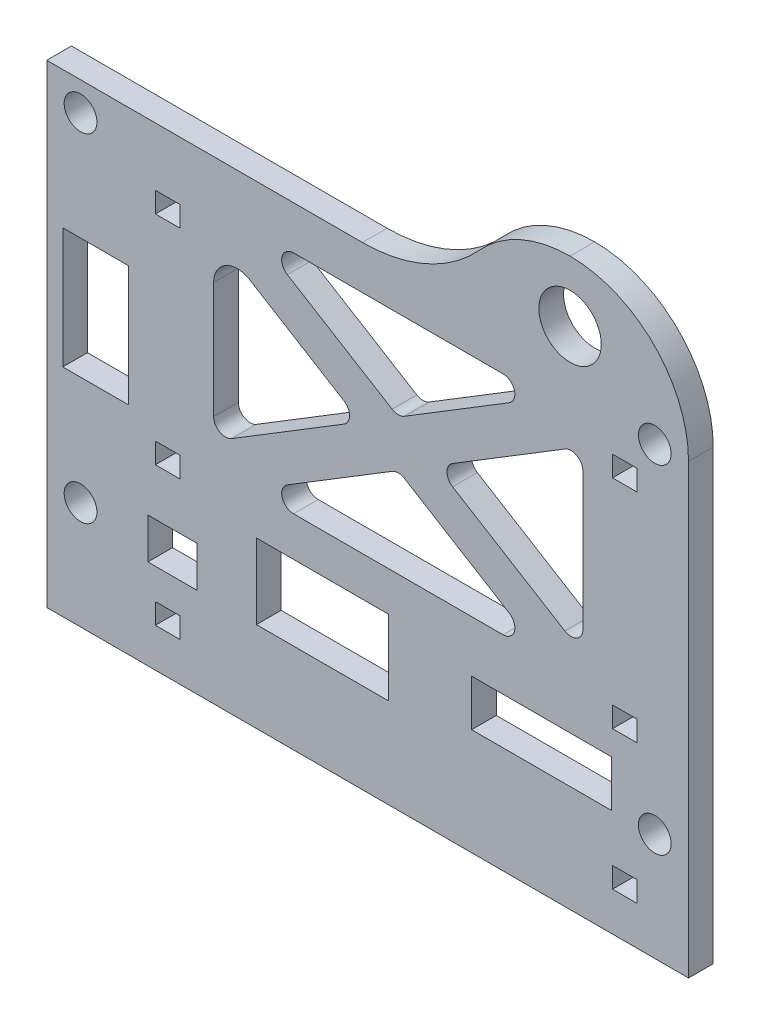
SolidWorks part; units mm, degrees
material "Beech"
ref_plane "Front Plane" through (0, 0, 0) normal (0, 0, 1) x (1, 0, 0)
ref_plane "Top Plane" through (0, 0, 0) normal (0, 1, 0) x (1, 0, 0)
ref_plane "Right Plane" through (0, 0, 0) normal (1, 0, 0) x (0, 0, -1)
sketch "Sketch1" plane through (0, 0, 0) normal (0, 0, 1) x (1, 0, 0)
  line L0 (-20.6375, 0) -> (20.6375, 0)
  line L2 (-20.6375, 0) -> (20.6375, 0)
  line L3 (-20.6375, 0) -> (-20.6375, -5.08)
  line L4 (-20.6375, -5.08) -> (20.6375, -5.08)
  line L5 (20.6375, 0) -> (20.6375, -5.08)
  line L44 (0, 14.605) -> (0, 24.13) construction
  line L46 (-20.6375, 0) -> (-20.6375, 25.4)
  line L47 (-20.6375, 25.4) -> (20.6375, 25.4)
  line L48 (20.6375, 0) -> (20.6375, 25.4)
  line L49 (-20.6375, 12.7) -> (20.6375, 12.7) construction
  circle A2 centre (-18.4658, 23.5585) radius 1.0541
  circle A3 centre (-18.4658, 1.8415) radius 1.0541
  circle A4 centre (18.4658, 1.8415) radius 1.0541
  circle A5 centre (18.4658, 23.5585) radius 1.0541
  point P0 (0, 0)
  point P56 (0, 12.7)
  point P60 (0, 25.4)
  dimension "D14" = 12.7
  dimension "D4" = 2.1082
  dimension "D2" = 5.08
  dimension "D3" = 25.4
  dimension "D12" = 41.275
  dimension "D5" = 2.1717
  dimension "D6" = 1.8415
extrude "Boss-Extrude1" add sketch "Sketch1" along normal blind 1.5875 contours L48 L47 L46 | L5 L0 L3 L4 region at (0, 12.7, 0) region at (0, -2.54, 0)
sketch "Sketch3" plane through (0, 0, 0) normal (0, 0, -1) x (-1, 0, 0)
  line L0 (-15.748, 20.3318) -> (-15.748, 21.6526) construction
  line L1 (-15.748, 21.6526) -> (-17.3355, 21.6526) construction
  line L2 (-17.3355, 21.6526) -> (-17.3355, 20.3318) construction
  line L3 (-17.3355, 20.3318) -> (-15.748, 20.3318) construction
  line L4 (-15.748, 6.3618) -> (-15.748, 7.6826) construction
  line L5 (-15.748, 7.6826) -> (-17.3355, 7.6826) construction
  line L6 (-17.3355, 7.6826) -> (-17.3355, 6.3618) construction
  line L7 (-17.3355, 6.3618) -> (-15.748, 6.3618) construction
  line L8 (-15.748, -2.579) -> (-15.748, -1.2582) construction
  line L9 (-15.748, -1.2582) -> (-17.3355, -1.2582) construction
  line L10 (-17.3355, -1.2582) -> (-17.3355, -2.579) construction
  line L11 (-17.3355, -2.579) -> (-15.748, -2.579) construction
  line L12 (13.6525, 20.3318) -> (13.6525, 21.6526) construction
  line L13 (13.6525, 21.6526) -> (12.065, 21.6526) construction
  line L14 (12.065, 21.6526) -> (12.065, 20.3318) construction
  line L15 (12.065, 20.3318) -> (13.6525, 20.3318) construction
  line L16 (13.6525, 6.3618) -> (13.6525, 7.6826) construction
  line L17 (13.6525, 7.6826) -> (12.065, 7.6826) construction
  line L18 (12.065, 7.6826) -> (12.065, 6.3618) construction
  line L19 (12.065, 6.3618) -> (13.6525, 6.3618) construction
  line L20 (13.6525, -2.579) -> (13.6525, -1.2582) construction
  line L21 (13.6525, -1.2582) -> (12.065, -1.2582) construction
  line L22 (12.065, -1.2582) -> (12.065, -2.579) construction
  line L23 (12.065, -2.579) -> (13.6525, -2.579) construction
  line L24 (-15.748, 20.3318) -> (-15.748, 21.6526)
  line L25 (-15.748, 21.6526) -> (-17.3355, 21.6526)
  line L26 (-17.3355, 21.6526) -> (-17.3355, 20.3318)
  line L27 (-17.3355, 20.3318) -> (-15.748, 20.3318)
  line L28 (-15.748, 6.3618) -> (-15.748, 7.6826)
  line L29 (-15.748, 7.6826) -> (-17.3355, 7.6826)
  line L30 (-17.3355, 7.6826) -> (-17.3355, 6.3618)
  line L31 (-17.3355, 6.3618) -> (-15.748, 6.3618)
  line L32 (-15.748, -2.579) -> (-15.748, -1.2582)
  line L33 (-15.748, -1.2582) -> (-17.3355, -1.2582)
  line L34 (-17.3355, -1.2582) -> (-17.3355, -2.579)
  line L35 (-17.3355, -2.579) -> (-15.748, -2.579)
  line L36 (13.6525, 20.3318) -> (13.6525, 21.6526)
  line L37 (13.6525, 21.6526) -> (12.065, 21.6526)
  line L38 (12.065, 21.6526) -> (12.065, 20.3318)
  line L39 (12.065, 20.3318) -> (13.6525, 20.3318)
  line L40 (13.6525, 6.3618) -> (13.6525, 7.6826)
  line L41 (13.6525, 7.6826) -> (12.065, 7.6826)
  line L42 (12.065, 7.6826) -> (12.065, 6.3618)
  line L43 (12.065, 6.3618) -> (13.6525, 6.3618)
  line L44 (13.6525, -2.579) -> (13.6525, -1.2582)
  line L45 (13.6525, -1.2582) -> (12.065, -1.2582)
  line L46 (12.065, -1.2582) -> (12.065, -2.579)
  line L47 (12.065, -2.579) -> (13.6525, -2.579)
extrude "Attachment Holes" cut sketch "Sketch3" against normal up to next
sketch "Sketch2" plane through (0, 0, 1.5875) normal (0, 0, 1) x (1, 0, 0)
  line L1 (15.748, 20.3318) -> (15.748, 21.6526) construction
  line L2 (-12.065, 21.6526) -> (-12.065, 20.3318) construction
  line L7 (15.6858, 1.7743) -> (15.6858, 4.7602)
  line L8 (15.6858, 4.7602) -> (6.6858, 4.7602)
  line L9 (6.6858, 4.7602) -> (6.6858, 1.7743)
  line L10 (6.6858, 1.7743) -> (15.6858, 1.7743)
  line L11 (15.6858, 1.7743) -> (15.6858, 4.7602)
  line L12 (1.3552, 5.5335) -> (-7.1538, 5.5335)
  line L13 (1.3552, 0.7075) -> (1.3552, 5.5335)
  line L14 (-7.1538, 0.7075) -> (1.3552, 0.7075)
  line L15 (-7.1538, 5.5335) -> (-7.1538, 0.7075)
  line L16 (1.3552, 5.5335) -> (-7.1538, 5.5335)
  line L17 (1.3552, 0.7075) -> (1.3552, 5.5335)
  line L18 (-7.1538, 0.7075) -> (1.3552, 0.7075)
  line L19 (-7.1538, 5.5335) -> (-7.1538, 0.7075)
  line L20 (-10.9638, 3.3237) -> (-14.1388, 3.3237)
  line L21 (-10.9638, 0.7075) -> (-10.9638, 3.3237)
  line L22 (-14.1388, 0.7075) -> (-10.9638, 0.7075)
  line L23 (-14.1388, 3.3237) -> (-14.1388, 0.7075)
  line L24 (-10.9638, 3.3237) -> (-14.1388, 3.3237)
  line L25 (-10.9638, 0.7075) -> (-10.9638, 3.3237)
  line L26 (-14.1388, 0.7075) -> (-10.9638, 0.7075)
  line L27 (-14.1388, 3.3237) -> (-14.1388, 0.7075)
  line L28 (-19.6078, 8.834) -> (-15.3878, 8.834)
  line L29 (-19.6078, 16.584) -> (-19.6078, 8.834)
  line L30 (-15.3878, 16.584) -> (-19.6078, 16.584)
  line L31 (-15.3878, 8.834) -> (-15.3878, 16.584)
  line L32 (-19.6078, 8.834) -> (-15.3878, 8.834)
  line L33 (-19.6078, 16.584) -> (-19.6078, 8.834)
  line L34 (-15.3878, 16.584) -> (-19.6078, 16.584)
  line L35 (-15.3878, 8.834) -> (-15.3878, 16.584)
  line L36 (15.6858, 4.7602) -> (6.6858, 4.7602)
  line L37 (6.6858, 4.7602) -> (6.6858, 1.7743)
  line L38 (6.6858, 1.7743) -> (15.6858, 1.7743)
  line L64 (-9.906, 21.1171) -> (11.4098, 8.0735)
  line L65 (-9.906, 22.606) -> (13.843, 22.606)
  line L66 (-9.906, 22.606) -> (-9.906, 8.0735)
  line L67 (-9.906, 8.0735) -> (13.843, 8.0735)
  line L68 (13.843, 22.606) -> (13.843, 8.0735)
  line L69 (-9.906, 22.606) -> (13.843, 8.0735) construction
  line L70 (-9.906, 8.0735) -> (13.843, 22.606) construction
  line L71 (-7.4728, 22.606) -> (13.843, 9.5624)
  line L72 (-7.4728, 8.0735) -> (13.843, 21.1171)
  line L73 (-9.906, 9.5624) -> (11.4098, 22.606)
  line L74 (-9.2431, 6.9902) -> (14.5059, 21.5227) construction
  line L75 (-10.5689, 9.1568) -> (13.1801, 23.6893) construction
  line L76 (-10.5689, 21.5227) -> (13.1801, 6.9902) construction
  line L77 (-9.2431, 23.6893) -> (14.5059, 9.1568) construction
  line L78 (-20.6375, 25.4) -> (20.6375, 25.4) construction
  point P30 (1.9685, 15.3398)
  dimension "D9" = 2.794
  dimension "D10" = 2.54
  dimension "D11" = 1.905
  dimension "D12" = 2.159
  dimension "D2" = 0
  dimension "D3" = 0
  dimension "D4" = 0
  dimension "D5" = 1.27
  dimension "D6" = 1.27
  dimension "D7" = 1.27
  dimension "D8" = 1.27
  dimension "D13" = 0
extrude "Cut-Extrude1" cut sketch "Sketch2" against normal up to surface (1.5875 mm away) contours L72 L67 L64 | L72 L71 L68 | L71 L73 L65 | L66 L73 L64 | L16 L19 L18 L17 | L32 L35 L34 L33 | L24 L27 L26 L25 | L37 L38 L11 L36 up to face at (-12.8587, -1.9186, 0)
fillet "Fillet8" radius 0.762 11 edges at (-7.4728, 8.0735, 0.7937) (-9.906, 9.5624, 0.7937) (11.4098, 8.0735, 0.7937) (13.843, 9.5624, 0.7937) (13.843, 21.1171, 0.7937) (11.4098, 22.606, 0.7937) (-7.4728, 22.606, 0.7937) (1.9685, 13.8508, 0.7937) (4.4017, 15.3398, 0.7937) (1.9685, 16.8287, 0.7937) (-0.4647, 15.3398, 0.7937)
fillet "Fillet9" radius 1.524 1 edges at (-9.906, 21.1171, 0.7937)
sketch "Sketch4" plane through (0, 0, 1.5875) normal (0, 0, 1) x (1, 0, 0)
  line L0 (13.0175, 31.3182) -> (13.0175, 24.8771) construction
  line L1 (-20.6375, 25.4) -> (20.6375, 25.4) construction
  line L2 (13.0175, 27.4066) -> (13.0175, 34.6576) construction
  line L3 (20.6375, -5.08) -> (20.6375, 25.4) construction
  line L4 (13.0175, 29.4132) -> (0.7292, 29.4132) construction
  line L7 (5.3975, 25.4) -> (5.3975, 25.0062)
  line L8 (5.3975, 25.0062) -> (20.6375, 25.0062)
  line L9 (20.6375, 25.0062) -> (20.6375, 25.4)
  circle A0 centre (13.0175, 27.4066) radius 2.0066
  arc A1 (20.6375, 25.4) -> (5.3975, 25.4) centre (13.0175, 23.4535) ccw
  dimension "D1" = 4.0132
  dimension "D3" = 1.905
  dimension "D2" = 7.62
extrude "Boss-Extrude3" add sketch "Sketch4" against normal up to surface (1.5875 mm away) up to face at (11.1858, 3.2672, 0)
fillet "Fillet10" radius 10.16 1 edges at (5.3975, 25.4, 0.7937)
fillet "Fillet11" radius 7.62 1 edges at (20.6375, 25.4, 0.7937)
